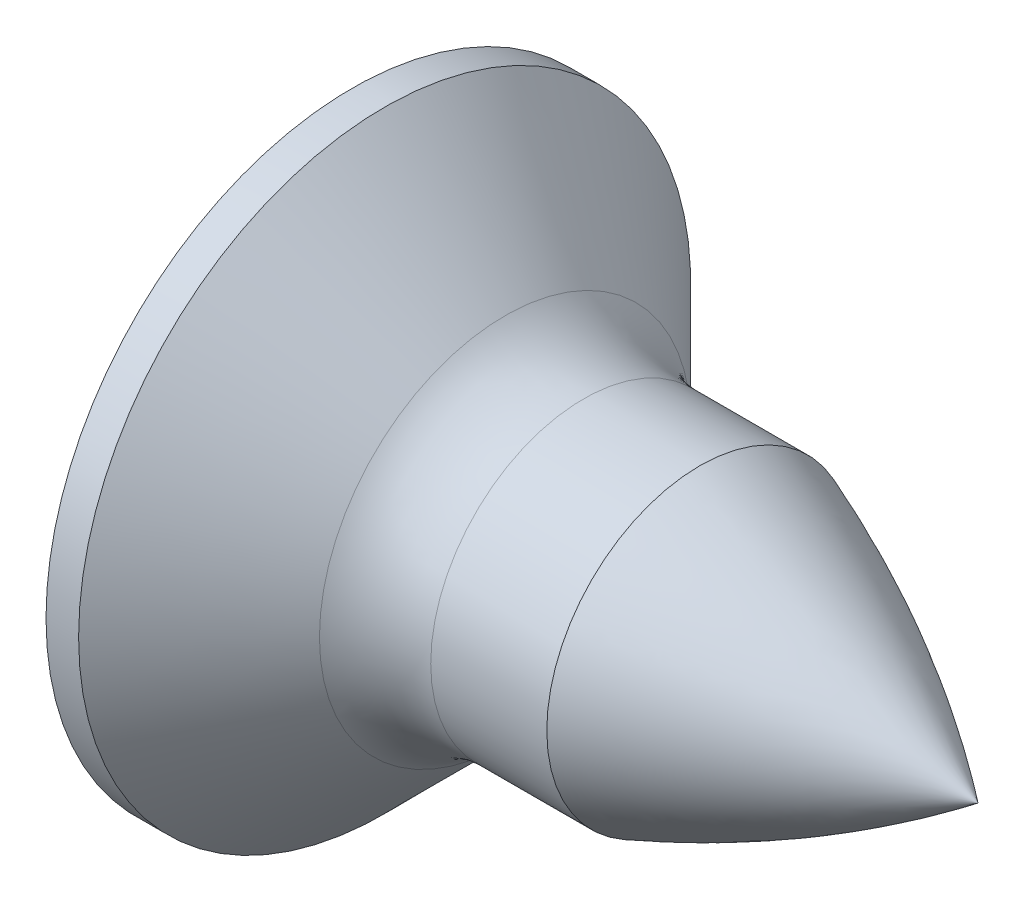
SolidWorks part; units mm, degrees
ref_plane "Front" through (0, 0, 0) normal (0, 0, 1) x (1, 0, 0)
ref_plane "Top" through (0, 0, 0) normal (0, 1, 0) x (1, 0, 0)
ref_plane "Right" through (0, 0, 0) normal (1, 0, 0) x (0, 0, -1)
sketch "Sketch1" plane through (0, 0, 0) normal (0, 0, 1) x (1, 0, 0)
  line L0 (-20.4182, 0) -> (11.3165, 0) construction
  line L1 (5, 0) -> (5, 1.1)
  line L2 (5, 1.1) -> (2.1657, 1.1)
  line L3 (2.4, 2.2) -> (2.4, -0.8442) construction
  line L4 (0.7343, 2.2) -> (0.5, 2.2)
  line L5 (5, 0) -> (0, 0)
  line L6 (1.6, 1.3343) -> (0.7343, 2.2)
  arc A0 (0.5, 2.2) -> (0, 0) centre (5.09, 0) ccw
  arc A1 (2.1657, 1.1) -> (1.6, 1.3343) centre (2.1657, 1.9) cw
  dimension "l" = 4.5
  dimension "D2" = 45
  dimension "k" = 1.1
revolve "Base" add sketch "Sketch1" angle 360 about L0
cosmetic thread "ThreadCosmetic1" [suppressed] parameters "D1"=2.6, "D2"=1.2
sketch "Sketch2" plane through (0, 0, 0) normal (1, 0, 0) x (0, 0, -1)
  line L0 (6.5369, 0) -> (-7.0008, 0) construction
  line L1 (0, 6.811) -> (0, -6.4314) construction
  line L2 (-0.22, 1.1) -> (0.22, 1.1)
  line L3 (0.22, 1.1) -> (0.22, 0.22)
  line L4 (0.22, 0.22) -> (1.1, 0.22)
  line L5 (1.1, 0.22) -> (1.1, -0.22)
  line L6 (0.22, -0.22) -> (1.1, -0.22)
  line L7 (0.22, -1.1) -> (0.22, -0.22)
  line L8 (-0.22, -1.1) -> (0.22, -1.1)
  line L9 (-0.22, -1.1) -> (-0.22, -0.22)
  line L10 (-0.22, -0.22) -> (-1.1, -0.22)
  line L11 (-1.1, 0.22) -> (-1.1, -0.22)
  line L12 (-0.22, 0.22) -> (-1.1, 0.22)
  line L13 (-0.22, 1.1) -> (-0.22, 0.22)
  point P5 (-1.1, 0)
  point P11 (1.1, 0)
  point P15 (0, -1.1)
  point P20 (0, 1.1)
  dimension "D2" = 2.2
  dimension "D3" = 0.44
  dimension "D4" = 0.44
extrude "CrossRecess" cut sketch "Sketch2" along normal blind 1.2
sketch "Sketch3" plane through (0, 0, 0) normal (1, 0, 0) x (0, 0, -1)
  line L0 (-4.5467, 4.5467) -> (4.5467, -4.5467) construction
  line L1 (-0.9538, 0.9538) -> (-0.22, 0.44)
  line L3 (-0.22, 0.44) -> (-0.22, 0.22)
  line L4 (-0.44, 0.22) -> (-0.22, 0.22)
  line L5 (-0.9538, 0.9538) -> (-0.44, 0.22)
  line L6 (7.069, 0) -> (-6.5067, 0) construction
  line L7 (0, 5.9645) -> (0, -0.3816) construction
  line L8 (0.9538, 0.9538) -> (0.44, 0.22)
  line L9 (0.44, 0.22) -> (0.22, 0.22)
  line L10 (0.22, 0.44) -> (0.22, 0.22)
  line L11 (0.9538, 0.9538) -> (0.22, 0.44)
  line L12 (0.9538, -0.9538) -> (0.22, -0.44)
  line L13 (0.22, -0.44) -> (0.22, -0.22)
  line L14 (0.44, -0.22) -> (0.22, -0.22)
  line L15 (0.9538, -0.9538) -> (0.44, -0.22)
  line L16 (-0.9538, -0.9538) -> (-0.44, -0.22)
  line L17 (-0.44, -0.22) -> (-0.22, -0.22)
  line L18 (-0.22, -0.44) -> (-0.22, -0.22)
  line L19 (-0.9538, -0.9538) -> (-0.22, -0.44)
  line L21 (0.22, 0.22) -> (1.1, 0.22) construction
  line L22 (0.22, 1.1) -> (0.22, 0.22) construction
  dimension "D1" = 20
  dimension "D2" = 0.22
extrude "Cut-Extrude2" [suppressed] cut sketch "Sketch3" along normal up to surface (2.25 mm away) up to face at (1.2, 0, 0)
sketch "Sketch4" plane through (0, 0, 0) normal (0, 0, 1) x (1, 0, 0)
  line L0 (35.6282, 0) -> (20.6612, 0) construction
  line L2 (3.4, -1.1) -> (4.2, -1.1)
  line L3 (4.2, -1.1) -> (5, -0.9)
  line L5 (5, -1.1) -> (5, 1.1) construction
  line L6 (3.4, -1.1) -> (3.4, -1.6)
  line L7 (3.4, -1.6) -> (5, -1.6)
  line L8 (5, -1.6) -> (5, -0.9)
  point P15 (4.2, -1.1)
  dimension "D2" = 0.8
  dimension "D1" = 2.2
  dimension "D3" = 0.2
  dimension "D4" = 0.5
revolve "Cut-Revolve1" [suppressed] cut sketch "Sketch4" angle 360 about L0
sketch "Sketch5" plane through (0, 0, 0) normal (0, 0, 1) x (1, 0, 0)
  line L0 (37.0407, 0) -> (13.7121, 0) construction
  line L2 (5, -1.1) -> (5, 1.1) construction
  line L3 (5, 0) -> (3, -1.1) construction
  line L6 (5, 0) -> (5.5, 0)
  line L7 (3, -1.1) -> (5, -1.1)
  line L8 (5.5, 0) -> (5.5, -1.1)
  line L9 (5.5, -1.1) -> (5, -1.1)
  arc A0 (5, 0) -> (3, -1.1) centre (0.1841, 6.388) cw
  dimension "D1" = 8
  dimension "D3" = 2.2
  dimension "D2" = 0.5
revolve "Cut-Revolve6" cut sketch "Sketch5" angle 360 about L0
draft "Draft1" type of draft neutral plane draft angle 30 neutral plane "Right" faces to draft 4 face at (0.6614, -1.1, 0) face at (0.6614, 0, -1.1) face at (0.6614, 0, 1.1) face at (0.6614, 1.1, 0) neutral plane through (0, 0, 0) neutral plane normal (1, 0, 0) reverse direction yes parameters "D1"=30
sketch "Sketch6" plane through (0, 0, 0) normal (0, 0, 1) x (1, 0, 0)
  line L0 (2.15, 1.6) -> (2.65, 1.6)
  line L1 (2.65, 1.6) -> (2.65, 1.1)
  line L2 (2.65, 1.1) -> (2.4, 0.667)
  line L3 (2.4, 0.667) -> (2.15, 1.1)
  line L4 (2.15, 1.1) -> (2.15, 1.6)
  line L5 (0, 0) -> (5.4654, 0) construction
  dimension "D1" = 2.2
  dimension "D2" = 0.5
  dimension "D3" = 0.8
revolve "Cut-Revolve10" [suppressed] cut sketch "Sketch6" angle 360 about L5
pattern_linear "LPattern10" [suppressed] count 4 spacing 0.6 along (1, 0, 0) of bodies 110
equation "\"D3@Sketch2\" = \"m@Sketch2\" / 5"
equation "\"D4@Sketch2\" = \"D3@Sketch2\""
equation "\"D2@Sketch2\" = \"m@Sketch2\""
equation "\"D2@Sketch3\" = \"m@Sketch2\" / 10"
equation "\"D3@Sketch4\" = \"yf@Sketch4\" / 8"
equation "\"D2@ThreadCosmetic1\" = \"st@Sketch1\" - 1"
equation "\"D1@Sketch5\" = \"yc@Sketch5\" * 4"
equation "\"D3@Sketch5\" = \"st@Sketch1\""
equation "\"D2@Sketch4\" = \"yf@Sketch4\" / 2"
equation "\"D1@Sketch4\" = \"st@Sketch1\""
equation "\"D1@ThreadCosmetic1\" = \"l@Sketch1\" - \"k@Sketch1\" - \"a@Sketch1\""
equation "\"D1@Sketch6\" = \"st@Sketch1\""
equation "\"D2@Sketch6\" =  ( \"D1@Sketch6\" - \"D2@ThreadCosmetic1\" )  / 2"
equation "\"D3@Sketch6\" = \"a@Sketch1\""
equation "\"D3@LPattern10\" = \"D2@Sketch6\" * 1.2"
equation "\"D1@LPattern10\" = \"D1@ThreadCosmetic1\" / \"D3@LPattern10\""
